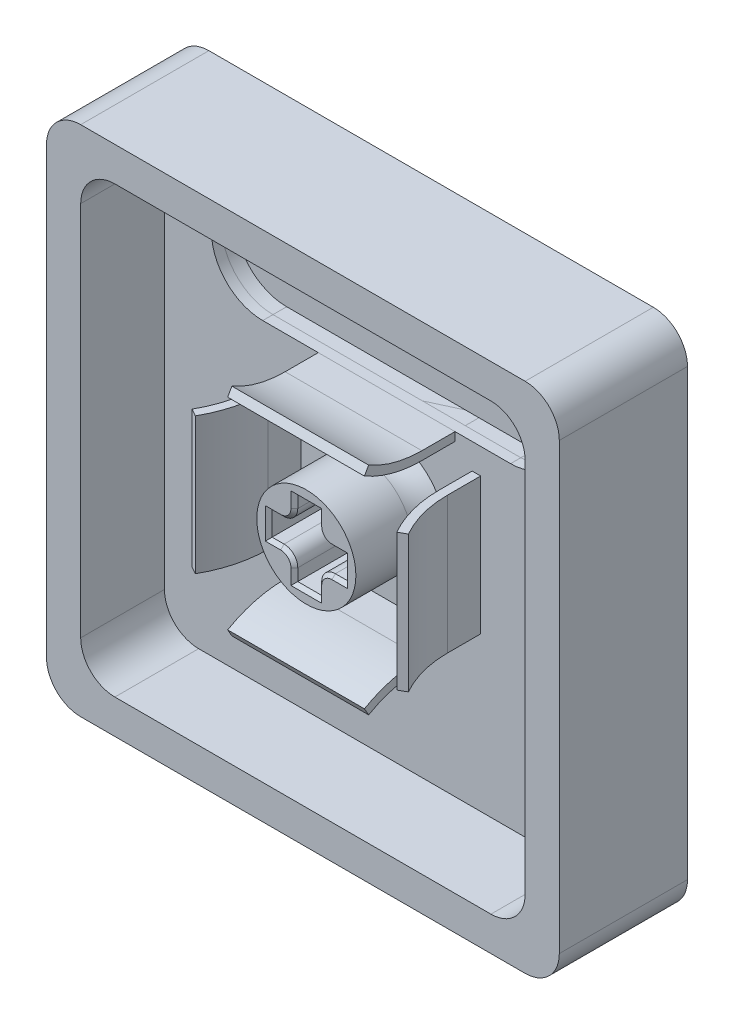
SolidWorks part; units mm, degrees
note: '?' marks a value the reader was unsure of. The reader was unsure of these and kept them because the rebuilt part matched: shared geometry of "草图1<6>", "草图1<7>".
other "标注1"
sketch "草图2" plane through (15, -15, 10) normal (0.3933, -0.7926, 0.466) x (0.9059, 0.4207, -0.0491)
ref_plane "前视基准面" through (0, 0, 0) normal (0, 0, 1) x (1, 0, 0)
ref_plane "上视基准面" through (0, 0, 0) normal (0, 1, 0) x (1, 0, 0)
ref_plane "右视基准面" through (0, 0, 0) normal (1, 0, 0) x (0, 0, -1)
sketch "草图1" plane through (0, 0, 0) normal (0, 0, 1) x (1, 0, 0)
  line L0 (-13, 15) -> (13, 15)
  line L1 (-11, 13) -> (11, 13)
  line L2 (-13, 11) -> (-13, -11)
  line L3 (-11, -13) -> (11, -13)
  line L4 (13, 11) -> (13, -11)
  line L5 (0, -13) -> (0, 13) construction
  line L6 (-13, 0) -> (13, 0) construction
  line L7 (15, 13) -> (15, -13)
  line L8 (-13, -15) -> (13, -15)
  line L9 (-15, 13) -> (-15, -13)
  line L10 (-13, -13) -> (13, -13) construction
  line L11 (-2.2, 0.7) -> (2.2, 0.7)
  line L12 (-2.2, 0.7) -> (-2.2, -0.7)
  line L13 (-2.2, -0.7) -> (2.2, -0.7)
  line L14 (2.2, 0.7) -> (2.2, -0.7)
  line L15 (0, -0.7) -> (0, 0.7) construction
  line L16 (-2.2, 0) -> (2.2, 0) construction
  line L17 (-0.7, 2.2) -> (0.7, 2.2)
  line L18 (-0.7, 2.2) -> (-0.7, -2.2)
  line L19 (-0.7, -2.2) -> (0.7, -2.2)
  line L20 (0.7, 2.2) -> (0.7, -2.2)
  line L21 (0, -2.2) -> (0, 2.2) construction
  line L22 (-0.7, 0) -> (0.7, 0) construction
  line L23 (13, 13) -> (13, -13) construction
  line L24 (-13, 13) -> (13, 13) construction
  line L25 (-13, 13) -> (-13, -13) construction
  line L26 (-15, 15) -> (-15, -15) construction
  line L27 (-15, -15) -> (15, -15) construction
  line L28 (15, 15) -> (15, -15) construction
  line L29 (-15, 15) -> (15, 15) construction
  line L36 (-13, 0) -> (-2.5, 0) construction
  circle A0 centre (0, 0) radius 2.9
  arc A1 (11, -13) -> (13, -11) centre (11, -11) ccw
  arc A2 (13, 11) -> (11, 13) centre (11, 11) ccw
  arc A3 (-13, 11) -> (-11, 13) centre (-11, 11) cw
  arc A4 (-13, -11) -> (-11, -13) centre (-11, -11) ccw
  arc A5 (-15, -13) -> (-13, -15) centre (-13, -13) ccw
  arc A6 (13, -15) -> (15, -13) centre (13, -13) ccw
  arc A7 (15, 13) -> (13, 15) centre (13, 13) ccw
  arc A8 (-15, 13) -> (-13, 15) centre (-13, 13) cw
  point P0 (0, 0)
  point P19 (13, -13)
  point P66 (0.0162, 0.0162)
  dimension "D4" = 5.8
  dimension "D9" = 2
  dimension "D1" = 30
  dimension "D2" = 30
  dimension "D5" = 4.4
  dimension "D6" = 1.4
  dimension "D7" = 4.4
  dimension "D8" = 1.4
  dimension "D3" = 2
extrude "凸台-拉伸1" add sketch "草图1" along normal blind 5.5 contours A8 L9 A5 L8 A6 L7 A7 L0 A4 L2 A3 L1 A2 L4 A1 L3
extrude "凸台-拉伸2" add sketch "草图1<6>" along normal blind 5.3 separate body contours A0 L17 L20 L11 L14 L13 L19 L18 L12
sketch "草图1<6>" plane through (0, 0, 0) normal (0, 0, 1) x (1, 0, 0) same geometry as "草图1"
extrude "凸台-拉伸3" add sketch "草图1<7>" against normal blind 2 contours L8 A6 L7 A7 L0 A8 L9 A5
sketch "草图1<7>" plane through (0, 0, 0) normal (0, 0, 1) x (1, 0, 0) same geometry as "草图1"
sketch "草图3" plane through (0, 0, 0) normal (0, 0, 1) x (1, 0, 0)
  line L8 (0.7, 0.7) -> (0.7, 2.2)
  line L10 (0.7, 0.7) -> (0.7, 2.2)
  line L15 (-0.7, 0.7) -> (-2.2, 0.7)
  line L16 (-2.2, 0.7) -> (-2.2, -0.7)
  line L17 (-2.2, -0.7) -> (-0.7, -0.7)
  line L19 (0.7, 2.2) -> (-0.7, 2.2)
  line L20 (0.7, 2.2) -> (-0.7, 2.2)
  line L21 (0.7, -0.7) -> (2.2, -0.7)
  line L22 (2.2, -0.7) -> (2.2, 0.7)
  line L23 (2.2, 0.7) -> (0.7, 0.7)
  line L27 (-0.7, 0.7) -> (-2.2, 0.7)
  line L28 (-2.2, 0.7) -> (-2.2, -0.7)
  line L29 (-2.2, -0.7) -> (-0.7, -0.7)
  line L33 (0.7, -0.7) -> (2.2, -0.7)
  line L34 (2.2, -0.7) -> (2.2, 0.7)
  line L35 (2.2, 0.7) -> (0.7, 0.7)
  line L36 (-0.7, 2.2) -> (-0.7, 0.7)
  line L37 (-0.7, 2.2) -> (-0.7, 0.7)
  line L38 (-0.7, -0.7) -> (-0.7, -2.2)
  line L39 (-0.7, -0.7) -> (-0.7, -2.2)
  line L40 (-0.7, -2.2) -> (0.7, -2.2)
  line L41 (-0.7, -2.2) -> (0.7, -2.2)
  line L42 (0.7, -2.2) -> (0.7, -0.7)
  line L43 (0.7, -2.2) -> (0.7, -0.7)
  dimension "D1" = 0
extrude "凸台-拉伸4" add sketch "草图3" along normal blind 2
sketch "草图5" plane through (0, 0, 0) normal (0, 0, 1) x (1, 0, 0)
  line L6 (7.25, 8.5) -> (-7.25, 8.5) construction
  line L7 (7.25, 5.5) -> (-7.25, 5.5)
  line L9 (7.25, 11.5) -> (-7.25, 11.5)
  line L10 (0, 0) -> (0, -50000) construction
  arc A0 (7.25, 5.5) -> (7.25, 11.5) centre (7.25, 8.5) ccw
  arc A1 (-7.25, 11.5) -> (-7.25, 5.5) centre (-7.25, 8.5) ccw
  point P2 (0, 8.5)
  dimension "D2" = 3
  dimension "D1" = 14.5
  dimension "D3" = 8.5
extrude "切除-拉伸1" cut sketch "草图5" against normal up to next
sketch "草图6" plane through (0, 0, -2) normal (0, 0, -1) x (-1, 0, 0)
  line L10 (7.25, 5.5) -> (-7.25, 5.5) construction
  line L11 (-7.25, 11.5) -> (7.25, 11.5) construction
  line L12 (7.25, 5.5) -> (-7.25, 5.5)
  line L13 (-7.25, 11.5) -> (7.25, 11.5)
  arc A0 (7.25, 5.5) -> (7.25, 11.5) centre (7.25, 8.5) ccw construction
  arc A1 (-7.25, 11.5) -> (-7.25, 5.5) centre (-7.25, 8.5) ccw construction
  arc A2 (7.25, 5.5) -> (7.25, 11.5) centre (7.25, 8.5) ccw
  arc A3 (-7.25, 11.5) -> (-7.25, 5.5) centre (-7.25, 8.5) ccw
extrude "凸台-拉伸6" add sketch "草图6" against normal blind 1.2 separate body
sketch "草图7" plane through (0, 0, 0) normal (0, 0, 1) x (1, 0, 0)
  line L0 (7.25, 5.5) -> (-7.25, 5.5) construction
  line L1 (7.25, 11.5) -> (-7.25, 11.5) construction
  line L2 (7.25, 5.5) -> (-7.25, 5.5)
  line L3 (7.25, 11.5) -> (-7.25, 11.5)
  line L4 (-13, 11) -> (-13, -11)
  line L5 (-11, -13) -> (11, -13)
  line L6 (13, -11) -> (13, 11)
  line L7 (11, 13) -> (-11, 13)
  line L8 (-13, 11) -> (-13, -11)
  line L9 (-11, -13) -> (11, -13)
  line L10 (13, -11) -> (13, 11)
  line L11 (11, 13) -> (-11, 13)
  circle A0 centre (0, 0) radius 2.9 construction
  circle A1 centre (0, 0) radius 2.9
  arc A2 (7.25, 5.5) -> (7.25, 11.5) centre (7.25, 8.5) ccw construction
  arc A3 (-7.25, 11.5) -> (-7.25, 5.5) centre (-7.25, 8.5) ccw construction
  arc A4 (-13, -11) -> (-11, -13) centre (-11, -11) ccw
  arc A5 (11, -13) -> (13, -11) centre (11, -11) ccw
  arc A6 (13, 11) -> (11, 13) centre (11, 11) ccw
  arc A7 (-11, 13) -> (-13, 11) centre (-11, 11) ccw
  arc A8 (-13, -11) -> (-11, -13) centre (-11, -11) ccw
  arc A9 (11, -13) -> (13, -11) centre (11, -11) ccw
  arc A10 (13, 11) -> (11, 13) centre (11, 11) ccw
  arc A11 (-11, 13) -> (-13, 11) centre (-11, 11) ccw
  arc A12 (7.25, 5.5) -> (7.25, 11.5) centre (7.25, 8.5) ccw
  arc A13 (-7.25, 11.5) -> (-7.25, 5.5) centre (-7.25, 8.5) ccw
  dimension "D1" = 0
ref_plane "基准面1" through (0, 0, 0) normal (0, 1, 0) x (1, 0, 0)
ref_axis "基准轴1" through (0, 0, 5.3) along (0, 0, -1)?
sketch "草图9" plane through (0, 0, 0) normal (0, 1, 0) x (1, 0, 0)
  line L0 (-15, 1.1634) -> (15, 1.1634) construction
  line L4 (15, -5.5) -> (13, -5.5)
  line L6 (15, -5.5) -> (13, -5.5) construction
  line L12 (13, -5.5) -> (-13, -5.5)
  line L14 (13, -5.5) -> (-13, -5.5) construction
  line L16 (-13, -5.5) -> (-15, -5.5)
  line L18 (-13, -5.5) -> (-15, -5.5) construction
  line L20 (5.8942, -5.9022) -> (6.3282, -5.6538)
  line L21 (5.5, 1.1634) -> (5.5, -2.5392)
  line L22 (5, 1.1634) -> (5, -2.5392)
  line L23 (0, 0) -> (0, 50000) construction
  line L24 (5.5, 1.1634) -> (5, 1.1634)
  line L29 (-15, -5.5) -> (-15, 2)
  line L30 (-15, -5.5) -> (-15, 2) construction
  line L31 (-15, 2) -> (-13, 2)
  line L32 (-15, 2) -> (-13, 2) construction
  line L33 (-13, 2) -> (13, 2)
  line L34 (-13, 2) -> (13, 2) construction
  line L35 (13, 2) -> (15, 2)
  line L36 (13, 2) -> (15, 2) construction
  line L37 (15, 2) -> (15, -5.5)
  line L38 (15, 2) -> (15, -5.5) construction
  arc A0 (5.5, -2.5392) -> (6.3282, -5.6538) centre (11.7708, -2.5392) ccw
  arc A1 (5, -2.5392) -> (5.8942, -5.9022) centre (11.7708, -2.5392) ccw
  point P41 (0, 1.1634)
  dimension "D1" = 0.5
  dimension "D2" = 0.5
  dimension "D3" = 5
extrude "凸台-拉伸9" add sketch "草图9" along normal mid plane 8 separate body
ref_plane "基准面3" through (0, 0, 0) normal (-0.7071, 0.7071, 0) x (0.7071, 0.7071, 0)
sketch "草图11" plane through (0, 0, 0) normal (-0.7071, 0.7071, 0) x (0.7071, 0.7071, 0)
  line L0 (13.4246, 2) -> (20.3848, 2) construction
  line L1 (20.3848, 2) -> (20.3848, -5.5) construction
  line L2 (20.3848, -5.5) -> (17.5563, -5.5) construction
  line L3 (17.5563, -5.5) -> (16.9706, -5.5) construction
  line L4 (16.9706, -5.5) -> (1.4142, -5.5) construction
  line L5 (1.4142, -5.5) -> (-1.4142, -5.5) construction
  line L6 (-1.4142, -5.5) -> (-16.9706, -5.5) construction
  line L7 (-16.9706, -5.5) -> (-17.5563, -5.5) construction
  line L8 (-17.5563, -5.5) -> (-20.3848, -5.5) construction
  line L9 (-20.3848, -5.5) -> (-20.3848, 2) construction
  line L10 (-20.3848, 2) -> (6.364, 2) construction
  line L11 (6.364, 2) -> (12.5511, 2) construction
  line L12 (12.5511, 2) -> (13.4246, 2) construction
  line L13 (14.3563, -0.0135) -> (14.3563, -0.6104)
  line L14 (15.5563, 0) -> (15.5563, -0.6104)
  line L15 (14.3563, -0.6104) -> (15.5563, -0.6104) construction
  line L17 (14.3563, -0.0135) -> (15.5563, 0)
  line L18 (15.5563, -0.6104) -> (15.5563, -2.2135)
  line L19 (15.5563, -2.2135) -> (12.7123, -2.2135)
  line L20 (12.7123, -2.2135) -> (12.7123, -1.0135)
  line L21 (12.7123, -1.0135) -> (14.3563, -1.0135)
  line L22 (14.3563, -1.0135) -> (14.3563, -0.6104)
  dimension "D1" = 1.2
  dimension "D2" = 1.2
  dimension "D3" = 1
extrude "凸台-拉伸11" [suppressed] add sketch "草图11" along normal mid plane 2 separate body
fillet "圆角4" radius 0.8 4 edges at (-0.7, 0.7, 3.65) (0.7, 0.7, 3.65) (-0.7, -0.7, 3.65) (0.7, -0.7, 3.65)
chamfer "倒角1" distance 0.2 angle 45 16 edges at (-0.7, 1.85, 5.3) (-1.85, 0.7, 5.3) (-2.2, 0, 5.3) (-1.85, -0.7, 5.3) (-0.7, -1.85, 5.3) (0, -2.2, 5.3) (0.7, -1.85, 5.3) (1.85, -0.7, 5.3) (2.2, 0, 5.3) (1.85, 0.7, 5.3) (0.7, 1.85, 5.3) (0, 2.2, 5.3) (-0.9343, -0.9343, 5.3) (0.9343, -0.9343, 5.3) (0.9343, 0.9343, 5.3) (-0.9343, 0.9343, 5.3)
fillet "圆角5" radius 2 1 edges at (2.9, 0, 0)
sketch "草图10" plane through (0, 0, 0) normal (0, 0, 1) x (1, 0, 0)
  line L0 (7.25, 5.5) -> (-7.25, 5.5) construction
  line L1 (7.25, 11.5) -> (-7.25, 11.5) construction
  line L2 (7.25, 5.5) -> (-7.25, 5.5)
  line L3 (7.25, 11.5) -> (-7.25, 11.5)
  line L4 (-13, 11) -> (-13, -11)
  line L5 (-11, -13) -> (11, -13)
  line L6 (13, -11) -> (13, 11)
  line L7 (11, 13) -> (-11, 13)
  line L8 (-13, 11) -> (-13, -11)
  line L9 (-11, -13) -> (11, -13)
  line L10 (13, -11) -> (13, 11)
  line L11 (11, 13) -> (-11, 13)
  arc A0 (7.25, 5.5) -> (7.25, 11.5) centre (7.25, 8.5) ccw construction
  arc A1 (-7.25, 11.5) -> (-7.25, 5.5) centre (-7.25, 8.5) ccw construction
  arc A2 (7.25, 5.5) -> (7.25, 11.5) centre (7.25, 8.5) ccw
  arc A3 (-7.25, 11.5) -> (-7.25, 5.5) centre (-7.25, 8.5) ccw
  arc A4 (-13, -11) -> (-11, -13) centre (-11, -11) ccw
  arc A5 (11, -13) -> (13, -11) centre (11, -11) ccw
  arc A6 (13, 11) -> (11, 13) centre (11, 11) ccw
  arc A7 (-11, 13) -> (-13, 11) centre (-11, 11) ccw
  arc A8 (-13, -11) -> (-11, -13) centre (-11, -11) ccw
  arc A9 (11, -13) -> (13, -11) centre (11, -11) ccw
  arc A10 (13, 11) -> (11, 13) centre (11, 11) ccw
  arc A11 (-11, 13) -> (-13, 11) centre (-11, 11) ccw
  dimension "D1" = 0
extrude "凸台-拉伸10" add sketch "草图10" along normal blind 0.6 separate body
pattern_circular "阵列(圆周)6" count 4 over 360 about axis through (0, 0, 0) along (0, 0, 1) of bodies 120
